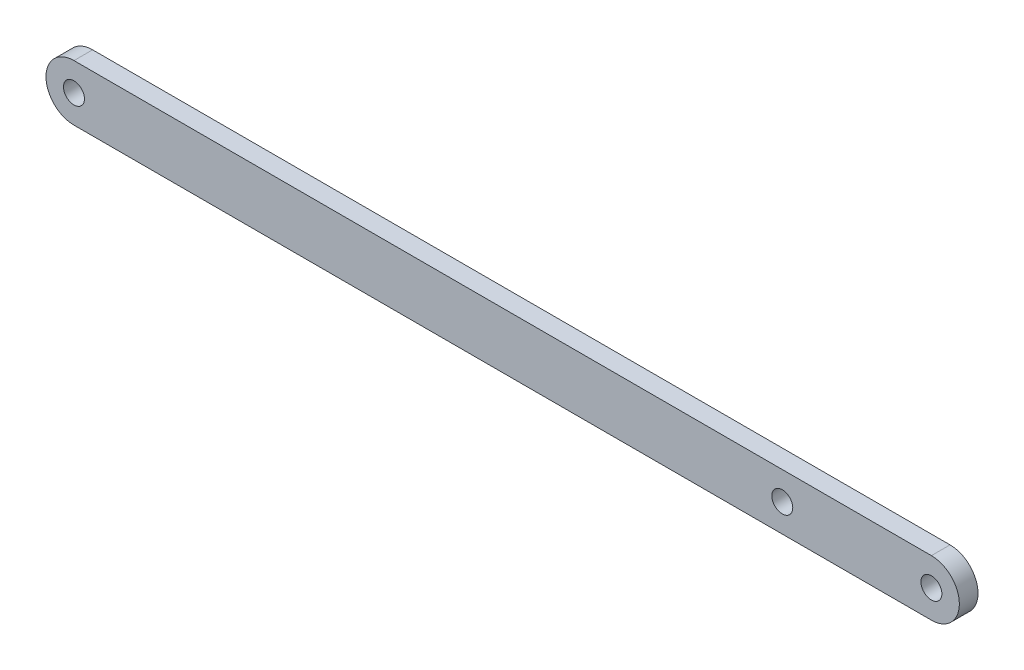
SolidWorks part; units mm, degrees
ref_plane "Front Plane" through (0, 0, 0) normal (0, 0, 1) x (1, 0, 0)
ref_plane "Top Plane" through (0, 0, 0) normal (0, 1, 0) x (1, 0, 0)
ref_plane "Right Plane" through (0, 0, 0) normal (1, 0, 0) x (0, 0, -1)
sketch "Sketch1" plane through (0, 0, 0) normal (0, 0, 1) x (1, 0, 0)
  line L0 (0, 0) -> (-120.65, 0) construction
  line L1 (0, -4.7625) -> (-120.65, -4.7625)
  line L2 (0, 4.7625) -> (-120.65, 4.7625)
  arc A0 (0, -4.7625) -> (0, 4.7625) centre (0, 0) ccw
  arc A1 (-120.65, 4.7625) -> (-120.65, -4.7625) centre (-120.65, 0) ccw
  point P3 (-60.325, 0)
extrude "Boss-Extrude1" add sketch "Sketch1" along normal blind 3.175
hole_wizard "9/64 (0.14063) Diameter Hole1" positions "Sketch3" profile "Sketch2" hole size "9/64" standard "ANSI Inch" end condition through all
sketch "Sketch3" plane through (0, 0, 3.175) normal (0, 0, 1) x (1, 0, 0)
  point P0 (0, 0)
  point P3 (-120.65, 0)
  dimension "D1" = 120.65
sketch "Sketch2" plane through (0, 0, 3.175) normal (1, 0, 0) x (0, -1, 0)
  line L0 (0, 0) -> (0, 3.175)
  line L1 (0, 3.175) -> (1.786, 3.175)
  line L2 (1.786, 3.175) -> (1.786, 0)
  line L5 (1.786, 0) -> (0, 0)
  line L11 (0, -6.35) -> (0, 107.95) construction
  dimension "Thru Hole Dia." = 3.572
  dimension "Thru Hole Depth" = 3.175
sketch "Sketch4" plane through (0, 0, 3.175) normal (0, 0, 1) x (1, 0, 0)
  line L0 (25.4, 4.7625) -> (0, 4.7625)
  line L1 (0, -4.7625) -> (25.4, -4.7625)
  arc A0 (0, -4.7625) -> (0, 4.7625) centre (0, 0) ccw
  arc A1 (25.4, -4.7625) -> (25.4, 4.7625) centre (25.4, 0) ccw
  dimension "D1" = 25.4
extrude "Boss-Extrude2" add sketch "Sketch4" against normal blind 3.175
hole_wizard "9/64 (0.14063) Diameter Hole2" positions "Sketch6" profile "Sketch5" hole size "9/64" standard "ANSI Inch" end condition through all
sketch "Sketch6" plane through (0, 0, 3.175) normal (0, 0, 1) x (1, 0, 0)
  arc A0 (25.4, -4.7625) -> (25.4, 4.7625) centre (25.4, 0) ccw construction
  point P0 (25.4, 0)
  point P1 (30.1625, 0)
  dimension "D1" = 4.7625
sketch "Sketch5" plane through (25.4, 0, 3.175) normal (1, 0, 0) x (0, -1, 0)
  line L0 (0, 0) -> (0, 3.175)
  line L1 (0, 3.175) -> (1.786, 3.175)
  line L2 (1.786, 3.175) -> (1.786, 0)
  line L5 (1.786, 0) -> (0, 0)
  line L11 (0, -6.35) -> (0, 107.95) construction
  dimension "Thru Hole Dia." = 3.572
  dimension "Thru Hole Depth" = 3.175
